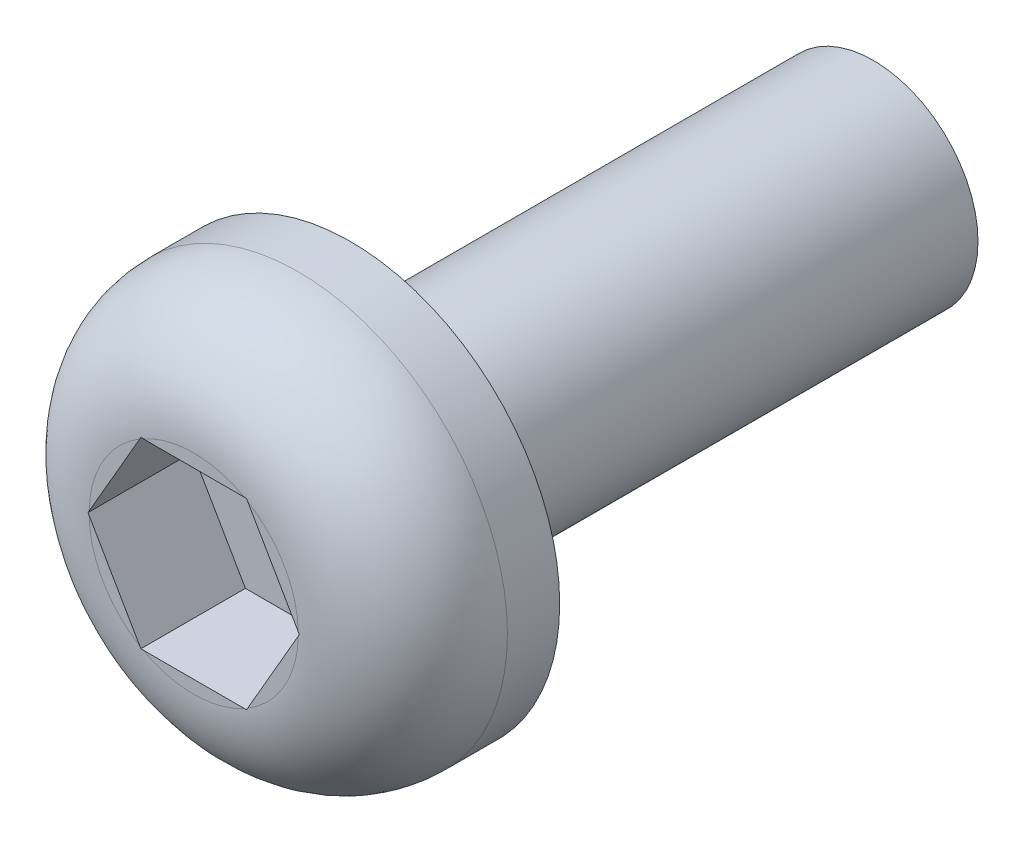
SolidWorks part; units mm, degrees
ref_plane "前视基准面" through (0, 0, 0) normal (0, 0, 1) x (1, 0, 0)
ref_plane "上视基准面" through (0, 0, 0) normal (0, 1, 0) x (1, 0, 0)
ref_plane "右视基准面" through (0, 0, 0) normal (1, 0, 0) x (0, 0, -1)
sketch "草图1" plane through (0, 0, 0) normal (0, 0, 1) x (1, 0, 0)
  circle A0 centre (0, 0) radius 2
  dimension "D1" = 4
extrude "凸台-拉伸1" add sketch "草图1" along normal blind 10
sketch "草图2" plane through (0, 0, 10) normal (0, 0, 1) x (1, 0, 0)
  circle A0 centre (0, 0) radius 4
  dimension "D1" = 8
extrude "凸台-拉伸2" add sketch "草图2" along normal blind 3
sketch "草图3" plane through (0, 0, 13) normal (0, 0, 1) x (1, 0, 0)
  line L1 (2.0207, 0) -> (1.0104, 1.75)
  line L2 (1.0104, 1.75) -> (-1.0104, 1.75)
  line L3 (-1.0104, 1.75) -> (-2.0207, 0)
  line L4 (-2.0207, 0) -> (-1.0104, -1.75)
  line L5 (-1.0104, -1.75) -> (1.0104, -1.75)
  line L6 (1.0104, -1.75) -> (2.0207, 0)
  circle A0 centre (0, 0) radius 1.75 construction
  dimension "D1" = 3.5
extrude "切除-拉伸1" cut sketch "草图3" against normal blind 2
fillet "圆角1" radius 2 1 edges at (4, 0, 13)
